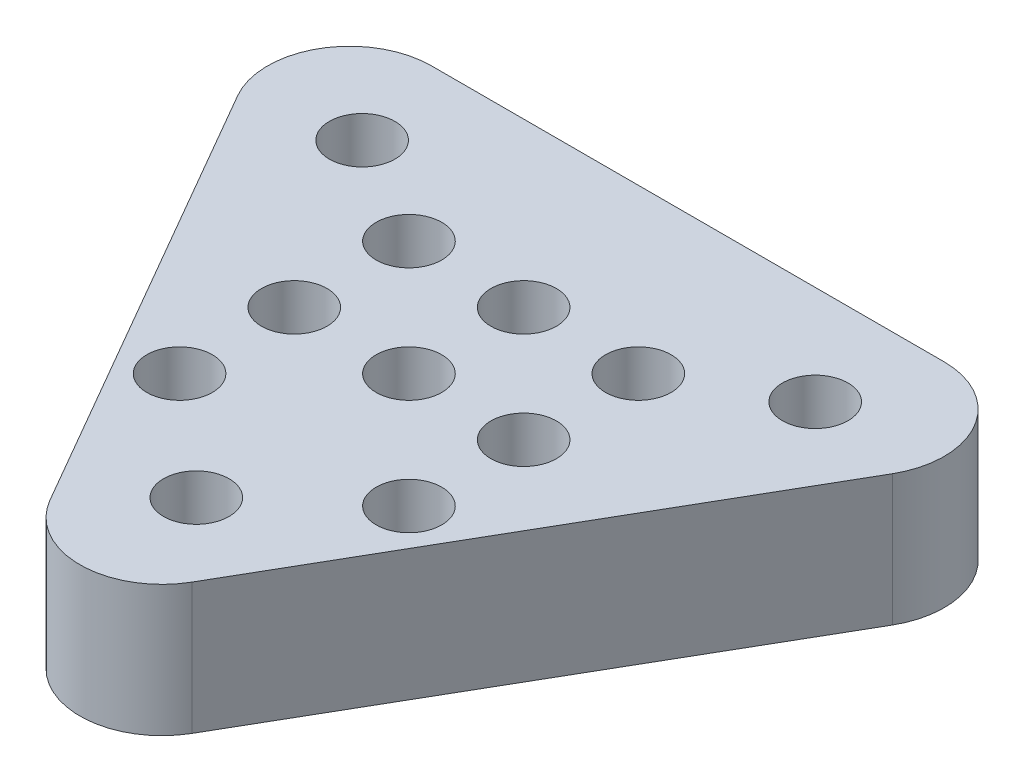
SolidWorks part; units mm, degrees
note: The reader was unsure of these and kept them because the rebuilt part matched: shared geometry of "Sketch1<3>".
material "Chrome Stainless Steel"
ref_plane "Front Plane" through (0, 0, 0) normal (0, 0, 1) x (1, 0, 0)
ref_plane "Top Plane" through (0, 0, 0) normal (0, 1, 0) x (1, 0, 0)
ref_plane "Right Plane" through (0, 0, 0) normal (1, 0, 0) x (0, 0, -1)
sketch "Sketch1" plane through (0, 0, 0) normal (0, 1, 0) x (1, 0, 0)
  line L0 (-5.186, 3.3162) -> (2.6377, -10.235)
  line L1 (6.9679, -10.235) -> (14.7916, 3.3162)
  line L2 (12.6266, 7.0662) -> (-3.021, 7.0662)
  line L3 (-1.2742, -3.4594) -> (15.2246, 6.0662) construction
  line L4 (4.8028, 7.0662) -> (4.8028, -11.985) construction
  line L5 (10.8797, -3.4594) -> (-5.6191, 6.0662) construction
  circle A0 centre (-2.1106, 4.0406) radius 2.3812
  circle A1 centre (-2.1106, 4.0406) radius 1
  circle A2 centre (11.7162, 4.0406) radius 1
  circle A3 centre (4.8028, -7.9338) radius 1
  circle A4 centre (4.8028, -7.9338) radius 2.3813
  circle A5 centre (11.7162, 4.0406) radius 2.3812
  circle A6 centre (1.2703, 2.0886) radius 1
  circle A7 centre (4.7703, 2.0886) radius 1
  circle A8 centre (8.2703, 2.0886) radius 1
  circle A9 centre (1.2703, -1.4114) radius 1
  circle A10 centre (4.7703, -1.4114) radius 1
  circle A11 centre (8.2703, -1.4114) radius 1
  circle A12 centre (1.2703, -4.9114) radius 1
  circle A13 centre (4.7703, -4.9114) radius 1 [skipped]
  circle A14 centre (8.2703, -4.9114) radius 1
  arc A15 (-5.186, 3.3162) -> (-3.021, 7.0662) centre (-3.021, 4.5662) cw
  arc A16 (14.7916, 3.3162) -> (12.6266, 7.0662) centre (12.6266, 4.5662) ccw
  arc A17 (6.9679, -10.235) -> (2.6377, -10.235) centre (4.8028, -8.985) cw
  point P9 (-7.3511, 7.0662)
  point P12 (4.8028, -13.985)
  point P22 (4.8028, 0.0491)
  dimension "D1" = 4.7625
  dimension "D5" = 2
  dimension "D9" = 4.7625
  dimension "D10" = 4.7625
  dimension "D11" = 2
  dimension "D12" = 2.5
  dimension "D2" = 300
  dimension "D3" = 60
  dimension "D4" = 24.3078
  dimension "D6" = 15
  dimension "D7" = 15
  dimension "D8" = 15
extrude "Extrude1" add sketch "Sketch1" along normal blind 4 contours A0 | A17 L1 A16 L2 A15 L0 A14 A12 A11 A10 A9 A8 A7 A6 A5 A4 A0 | A5 | A4
extrude "Extrude4" cut sketch "Sketch1<3>" along normal blind 2 contours A4 | A5
sketch "Sketch1<3>" plane through (0, 0, 0) normal (0, 1, 0) x (1, 0, 0) same geometry as "Sketch1"
sketch "Sketch2" plane through (0, 0, 0) normal (1, 0, 0) x (0, 0, -1)
  circle A0 centre (-7.9111, -0.3368) radius 2.3813 construction
  dimension "D1" = 4.7625
  dimension "BallDiameter" = 10
